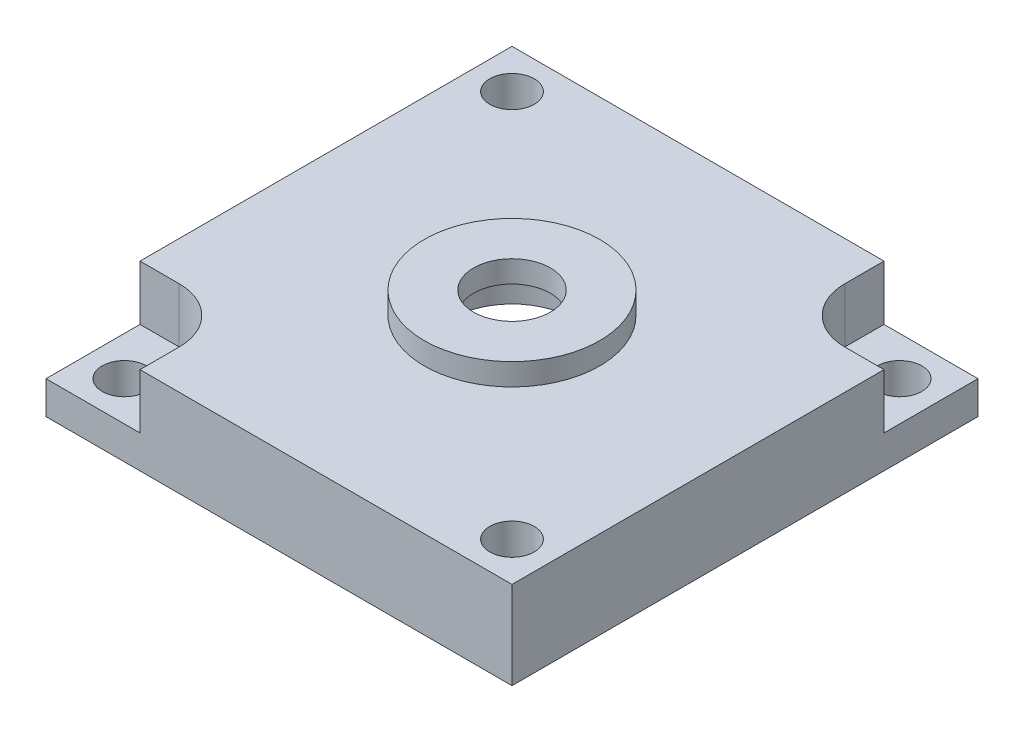
SolidWorks part; units mm, degrees
ref_plane "前视基准面" through (0, 0, 0) normal (0, 0, 1) x (1, 0, 0)
ref_plane "上视基准面" through (0, 0, 0) normal (0, 1, 0) x (1, 0, 0)
ref_plane "右视基准面" through (0, 0, 0) normal (1, 0, 0) x (0, 0, -1)
sketch "草图1" plane through (0, 0, 0) normal (0, 1, 0) x (1, 0, 0)
  line L1 (-21.25, -21.25) -> (21.25, -21.25)
  line L2 (-21.25, -21.25) -> (-21.25, 21.25)
  line L3 (-21.25, 21.25) -> (21.25, 21.25)
  line L4 (21.25, -21.25) -> (21.25, 21.25)
  line L5 (-21.25, -21.25) -> (21.25, 21.25) construction
  line L6 (-21.25, 21.25) -> (21.25, -21.25) construction
  circle A0 centre (0, 0) radius 18.5
  circle A1 centre (0, 0) radius 25 construction
  circle A2 centre (-17.6777, 17.6777) radius 2.025
  circle A3 centre (17.6777, 17.6777) radius 2.025
  circle A4 centre (17.6777, -17.6777) radius 2.025
  circle A5 centre (-17.6777, -17.6777) radius 2.025
  circle A6 centre (0, 0) radius 5.515
  point P19 (0, 0)
  dimension "D1" = 37
  dimension "D3" = 50
  dimension "D4" = 4.05
  dimension "D6" = 11.03
  dimension "D2" = 42.5
  dimension "D5" = 4
extrude "凸台-拉伸1" add sketch "草图1" along normal blind 5 contours L1 L4 L3 L2 A5 A4 A3 A2 A0 region at (-20.649, 0, 0)
extrude "凸台-拉伸2" add sketch "草图1<3>" along normal blind 3 from surface contours A0 A6 | L1 L4 L3 L2 A5 A4 A3 A2 A0 region at (-20.649, 0, 0) region at (-17.9767, 0, 0) starting at face at (-17.6777, 5, 19.7027)
sketch "草图1<3>" plane through (0, 0, 0) normal (0, 1, 0) x (1, 0, 0) same geometry as "草图1"
sketch "草图2" plane through (0, 8, 0) normal (0, 1, 0) x (1, 0, 0)
  line L0 (-17.6777, -12.6777) -> (-21.25, -12.6777)
  line L1 (-21.25, 21.25) -> (-21.25, -21.25) construction
  line L2 (-12.6777, -17.6777) -> (-12.6777, -21.25)
  line L3 (21.25, -21.25) -> (-21.25, -21.25) construction
  line L4 (-21.25, -12.6777) -> (-21.25, -21.25)
  line L5 (-21.25, -21.25) -> (-12.6777, -21.25)
  line L6 (21.25, 21.25) -> (12.6777, 21.25)
  line L7 (12.6777, 17.6777) -> (12.6777, 21.25)
  line L8 (17.6777, 12.6777) -> (21.25, 12.6777)
  line L9 (21.25, 12.6777) -> (21.25, 21.25)
  arc A1 (-12.6777, -17.6777) -> (-17.6777, -12.6777) centre (-17.6777, -17.6777) ccw
  arc A2 (12.6777, 17.6777) -> (17.6777, 12.6777) centre (17.6777, 17.6777) ccw
  point P22 (0, 0)
  dimension "D1" = 5
  dimension "D2" = 2
extrude "切除-拉伸1" cut sketch "草图2" against normal blind 5
sketch "草图3" plane through (0, 8, 0) normal (0, 1, 0) x (1, 0, 0)
  circle A0 centre (0, 0) radius 3.5
  circle A2 centre (0, 0) radius 8
  dimension "D1" = 16
  dimension "D2" = 7
extrude "凸台-拉伸3" add sketch "草图3" along normal blind 2
